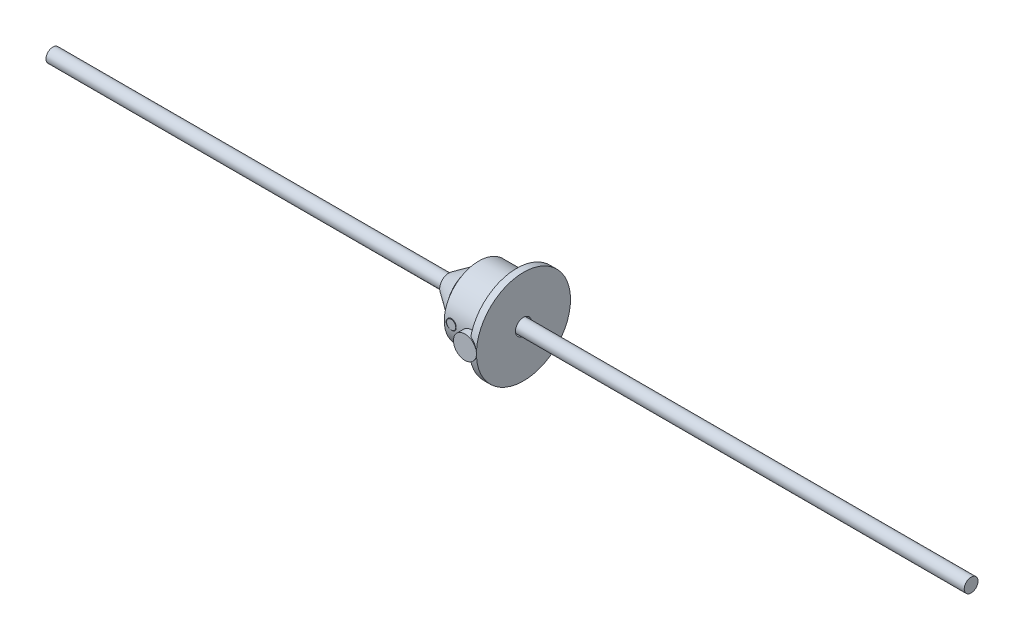
SolidWorks part; units mm, degrees
other "RD S Gear Outer"
other "RD L Gear Left"
other "RD L Gear Right"
other "RD Ring Gear"
other "RD S Gear Inner"
ref_plane "Front Plane" through (0, 0, 0) normal (0, 0, 1) x (1, 0, 0)
ref_plane "Top Plane" through (0, 0, 0) normal (0, 1, 0) x (1, 0, 0)
ref_plane "Right Plane" through (0, 0, 0) normal (1, 0, 0) x (0, 0, -1)
sketch "Top View Layout" plane through (0, 0, 0) normal (0, 1, 0) x (1, 0, 0)
  line L0 (-100, 125) -> (100, 125)
  line L1 (0, 125) -> (0, -125)
  line L2 (-100, -125) -> (100, -125)
  line L3 (0, -15) -> (35, -15) construction
  line L4 (35, -15) -> (35, -125) construction
  line L5 (2.5, 114.75) -> (2.5, 135.25) construction
  line L6 (-2.5, 114.75) -> (2.5, 114.75) construction
  line L7 (-8.75, 127) -> (-2.75, 127) construction
  line L8 (-2.5, 114.75) -> (2.5, 114.75) construction
  line L9 (-2.5, 114.75) -> (-2.5, 116.25) construction
  line L10 (-2.5, 116.25) -> (2.5, 116.25) construction
  line L11 (2.5, 114.75) -> (2.5, 116.25) construction
  line L12 (2.5, 135.25) -> (1, 135.25) construction
  line L13 (2.5, 135.25) -> (2.5, 114.75) construction
  line L14 (2.5, 114.75) -> (1, 114.75) construction
  line L15 (1, 135.25) -> (1, 114.75) construction
  line L16 (-4.25, 128.5) -> (-2.75, 128.5) construction
  line L17 (-4.25, 128.5) -> (-4.25, 121.5) construction
  line L18 (-4.25, 121.5) -> (-2.75, 121.5) construction
  line L19 (-2.75, 128.5) -> (-2.75, 121.5) construction
  line L20 (-4.25, 128.5) -> (-2.75, 121.5) construction
  line L21 (-4.25, 121.5) -> (-2.75, 128.5) construction
  line L22 (-8.75, 128.5) -> (-7.25, 128.5) construction
  line L23 (-8.75, 128.5) -> (-8.75, 121.5) construction
  line L24 (-8.75, 121.5) -> (-7.25, 121.5) construction
  line L25 (-7.25, 128.5) -> (-7.25, 121.5) construction
  line L26 (-8.75, 128.5) -> (-7.25, 121.5) construction
  line L27 (-8.75, 121.5) -> (-7.25, 128.5) construction
  line L28 (-8.75, 123) -> (-2.75, 123) construction
  point P8 (0, 114.75)
  point P9 (0, 0)
  point P11 (2.5, 125)
  point P16 (2.5, 125)
  point P19 (0, 114.75)
  point P23 (-3.5, 125)
  point P28 (-8, 125)
  point P37 (0, 0)
  point P38 (0, 0)
  dimension "D1" = 250
  dimension "D2" = 200
  dimension "D3" = 35
  dimension "D4" = 15
  dimension "D5" = 5
  dimension "D6" = 20.5
  dimension "D7" = 1.5
  dimension "D8" = 1.5
  dimension "D9" = 1.5
  dimension "D10" = 7
  dimension "D11" = 3.5
  dimension "D12" = 8
  dimension "D13" = 1.5
  dimension "D14" = 1.5
ref_plane "Left" through (100, 0, 0) normal (-1, 0, 0) x (0, 0, 1)
ref_plane "Right" through (-100, 0, 0) normal (-1, 0, 0) x (0, 0, 1)
sketch "Left Wheels" plane through (100, 0, 0) normal (-1, 0, 0) x (0, 0, 1)
  circle A0 centre (125, 0) radius 25
  circle A1 centre (-125, 0) radius 25
  point P4 (0, 0)
  point P6 (0, 0)
  point P8 (0, 0)
  point P9 (0, 0)
  point P10 (0, 0)
  dimension "D1" = 50
  dimension "D2" = 50
sketch "Right Wheels" plane through (-100, 0, 0) normal (-1, 0, 0) x (0, 0, 1)
  circle A0 centre (-125, 0) radius 25 construction
  circle A1 centre (125, 0) radius 25 construction
  circle A2 centre (-125, 0) radius 25
  circle A3 centre (125, 0) radius 25
  point P6 (0, 0)
ref_plane "Rear Differential Pinion Plane" through (0, 0, -114.75) normal (0, 0, 1) x (1, 0, 0)
sketch "Rear Differential Pinion Profile" plane through (0, 0, -114.75) normal (0, 0, 1) x (1, 0, 0)
  circle A0 centre (0, 0) radius 2.5
ref_plane "Rear Differential Ring Gear Plane" through (2.5, 0, 0) normal (1, 0, 0) x (0, 0, -1)
ref_plane "Rear Axle" through (0, 0, -125) normal (0, 0, 1) x (1, 0, 0)
sketch "Rear Differential Ring Gear Profile" plane through (2.5, 0, 0) normal (1, 0, 0) x (0, 0, -1)
  line L0 (114.75, 0) -> (135.25, 0) construction
  circle A0 centre (125, 0) radius 10.25
extrude "Rear Differential Pinion" add sketch "Rear Differential Pinion Profile" against normal blind 1.5 contours A0
extrude "Rear Differential Ring Gear" add sketch "Rear Differential Ring Gear Profile" against normal blind 1.5 separate body contours A0
ref_plane "RD Inner L Gear Plane" through (-2.75, 0, 0) normal (1, 0, 0) x (0, 0, -1)
ref_plane "RD Outer L Gear Plane" through (-8.75, 0, 0) normal (1, 0, 0) x (0, 0, -1)
sketch "RD Inner L Gear Profile" plane through (-2.75, 0, 0) normal (1, 0, 0) x (0, 0, -1)
  circle A0 centre (125, 0) radius 3.5
  point P2 (0, 0)
sketch "RD Outer L Gear Profile" plane through (-8.75, 0, 0) normal (1, 0, 0) x (0, 0, -1)
  line L0 (128.5, 0) -> (121.5, 0) construction
  circle A0 centre (125, 0) radius 3.5
ref_plane "RD Inner S Gear Plane" through (0, 0, -121.5) normal (0, 0, 1) x (1, 0, 0)
ref_plane "RD Outer S Gear Plane" through (0, 0, -128.5) normal (0, 0, 1) x (1, 0, 0)
sketch "RD Inner S Gear Profile" plane through (0, 0, -121.5) normal (0, 0, 1) x (1, 0, 0)
  line L0 (-8.75, 0) -> (-7.25, 0) construction
  circle A0 centre (-5.75, 0) radius 3
  point P3 (0, 0)
sketch "RD Outer S Gear Profile" plane through (0, 0, -128.5) normal (0, 0, 1) x (1, 0, 0)
  line L0 (-8.75, 0) -> (-7.25, 0) construction
  circle A2 centre (-5.75, 0) radius 3
  point P2 (0, 0)
extrude "RD Outer L Gear Extrude" add sketch "RD Outer L Gear Profile" along normal blind 1.5 separate body contours A0
extrude "RD Inner L Gear Extrude" add sketch "RD Inner L Gear Profile" against normal blind 1.5 separate body contours A0
extrude "RD Outer S Gear Extrude" add sketch "RD Outer S Gear Profile" along normal blind 1.5 separate body contours A2
extrude "RD Inner S Gear Extrude" add sketch "RD Inner S Gear Profile" against normal blind 1.5 separate body contours A0
sketch "RD Ring Gear Case Profile" plane through (1, 0, 0) normal (-1, 0, 0) x (0, 0, 1)
  line L0 (-121.5, 3.2113) -> (-121.5, -3.2113)
  line L1 (-128.5, 3.2113) -> (-128.5, -3.2113)
  line L2 (-121.5, 6.6332) -> (-121.5, 3.2113) construction
  line L3 (-128.5, 6.6332) -> (-128.5, 3.2113) construction
  line L4 (-121.5, -3.2113) -> (-121.5, -6.6332) construction
  line L5 (-128.5, -3.2113) -> (-128.5, -6.6332) construction
  circle A0 centre (-125, 0) radius 7.5
  arc A1 (-121.5, 3.2113) -> (-128.5, 3.2113) centre (-125, 0) ccw
  arc A2 (-121.5, -3.2113) -> (-121.5, 3.2113) centre (-125, 0) ccw construction
  arc A3 (-128.5, 3.2113) -> (-128.5, -3.2113) centre (-125, 0) ccw construction
  arc A4 (-128.5, -3.2113) -> (-121.5, -3.2113) centre (-125, 0) ccw
  point P7 (-121.5, 0)
  dimension "D1" = 15
  dimension "D2" = 9.5
extrude "RD Ring Gear Case " add sketch "RD Ring Gear Case Profile" along normal blind 8.25
sketch "Sketch11" plane through (-7.25, 0, 0) normal (-1, 0, 0) x (0, 0, 1)
  circle A0 centre (-125, 0) radius 5.5
  circle A1 centre (-125, 0) radius 4.75
  arc A2 (-121.5, 3.2113) -> (-128.5, 3.2113) centre (-125, 0) ccw construction
  dimension "D1" = 11
extrude "Boss-Extrude8" add sketch "Sketch11" along normal up to vertex up to point (-8.75, 0, -128.5)
fillet "Fillet1" radius 2 1 edges at (-7.25, 0, -119.5)
sketch "Sketch12" plane through (0, 0, -125) normal (0, 0, 1) x (1, 0, 0)
  line L0 (-8.75, 0) -> (-13.75, 0) construction
  line L1 (-8.75, 0) -> (-7.25, 0) construction
  line L2 (-8.75, 0) -> (-7.25, 0) construction
  line L3 (-100, 0) -> (100, 0) construction
  line L4 (-100, 0) -> (100, 0) construction
  line L5 (-8.75, 5.5) -> (-8.75, -5.5) construction
  line L6 (-13.75, 0) -> (-13.75, 2)
  line L7 (-13.75, 2) -> (-8.75, 5.5)
  line L8 (-13.75, 0) -> (-8.75, 0)
  line L9 (-8.75, 0) -> (-8.75, 5.5)
  point P15 (-13.75, 1)
  dimension "D1" = 5
  dimension "D2" = 2
revolve "Revolve1" add sketch "Sketch12" angle 360 about L0
sketch "Sketch13" plane through (2.5, 0, 0) normal (1, 0, 0) x (0, 0, -1)
  circle A0 centre (125, 0) radius 1.75
  dimension "D1" = 3.5
extrude "Cut-Extrude1" cut sketch "Sketch13" against normal through all
sketch "Sketch14" plane through (0, 0, -121.5) normal (0, 0, 1) x (1, 0, 0)
  circle A0 centre (-5.75, 0) radius 1
  dimension "D1" = 2
extrude "Boss-Extrude9" add sketch "Sketch14" along normal blind 4 separate body
sketch "Sketch15" plane through (0, 0, -121.5) normal (0, 0, 1) x (1, 0, 0)
  circle A0 centre (-5.75, 0) radius 1.1
  dimension "D1" = 2.2
extrude "Cut-Extrude2" cut sketch "Sketch15" against normal through all both and the other way through all
extrude "Boss-Extrude10" add sketch "Sketch14<2>" against normal blind 4 from surface starting at face at (-2.75, 0, -128.5)
sketch "Sketch14<2>" plane through (0, 0, -121.5) normal (0, 0, 1) x (1, 0, 0) same geometry as "Sketch14"
sketch "Sketch16" plane through (-8.75, 0, 0) normal (-1, 0, 0) x (0, 0, 1)
  circle A0 centre (-125, 0) radius 1.5
  dimension "D1" = 3
extrude "Boss-Extrude11" add sketch "Sketch16" along normal up to vertex (91.25 mm away) up to point (-100, 0, -125)
sketch "Sketch17" plane through (-2.75, 0, 0) normal (1, 0, 0) x (0, 0, -1)
  circle A0 centre (125, 0) radius 1.5 construction
  circle A1 centre (125, 0) radius 1.5
extrude "Boss-Extrude12" add sketch "Sketch17" along normal up to vertex (102.75 mm away) up to point (100, 0, -125)
